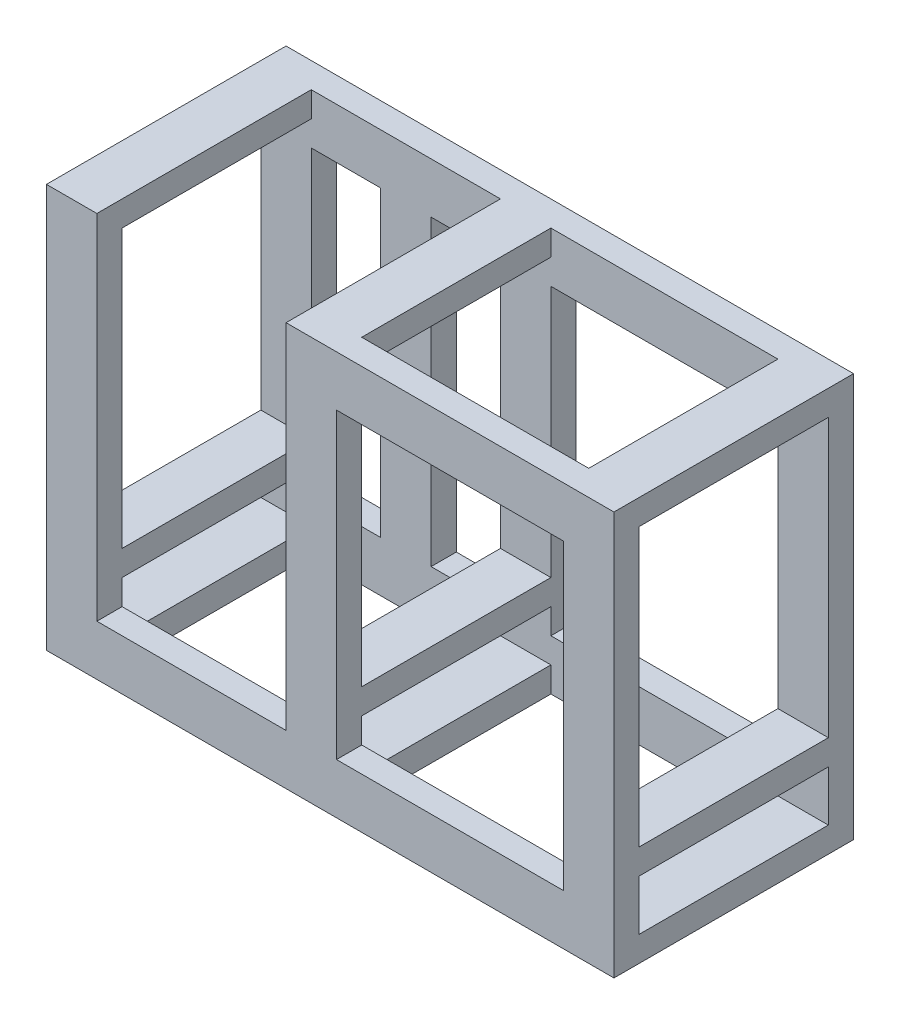
SolidWorks part; units mm, degrees
ref_plane "Front Plane" through (0, 0, 0) normal (0, 0, 1) x (1, 0, 0)
ref_plane "Top Plane" through (0, 0, 0) normal (0, 1, 0) x (1, 0, 0)
ref_plane "Right Plane" through (0, 0, 0) normal (1, 0, 0) x (0, 0, -1)
sketch "Sketch1" plane through (0, 0, 0) normal (0, 1, 0) x (1, 0, 0)
  line L1 (0, 0) -> (50.8, 0)
  line L2 (0, 0) -> (0, 25.4)
  line L3 (0, 25.4) -> (50.8, 25.4)
  line L4 (50.8, 0) -> (50.8, 25.4)
  line L5 (50.8, 0) -> (279.4, 0)
  line L6 (50.8, 0) -> (50.8, 25.4)
  line L7 (50.8, 25.4) -> (279.4, 25.4)
  line L8 (279.4, 0) -> (279.4, 25.4)
  line L9 (279.4, 0) -> (330.2, 0)
  line L10 (279.4, 0) -> (279.4, 25.4)
  line L11 (279.4, 25.4) -> (330.2, 25.4)
  line L12 (330.2, 0) -> (330.2, 25.4)
  line L13 (330.2, 25.4) -> (279.4, 25.4)
  line L14 (330.2, 25.4) -> (330.2, 215.9)
  line L15 (330.2, 215.9) -> (279.4, 215.9)
  line L16 (279.4, 25.4) -> (279.4, 215.9)
  line L17 (330.2, 215.9) -> (279.4, 215.9)
  line L18 (330.2, 215.9) -> (330.2, 241.3)
  line L19 (330.2, 241.3) -> (279.4, 241.3)
  line L20 (279.4, 215.9) -> (279.4, 241.3)
  line L21 (279.4, 241.3) -> (50.8, 241.3)
  line L22 (279.4, 241.3) -> (279.4, 215.9)
  line L23 (279.4, 215.9) -> (50.8, 215.9)
  line L24 (50.8, 241.3) -> (50.8, 215.9)
  line L25 (50.8, 241.3) -> (0, 241.3)
  line L26 (50.8, 241.3) -> (50.8, 215.9)
  line L27 (50.8, 215.9) -> (0, 215.9)
  line L28 (0, 241.3) -> (0, 215.9)
  line L29 (0, 215.9) -> (50.8, 215.9)
  line L30 (0, 215.9) -> (0, 25.4)
  line L31 (0, 25.4) -> (50.8, 25.4)
  line L32 (50.8, 215.9) -> (50.8, 25.4)
  line L33 (0, 25.4) -> (-190.5, 25.4)
  line L34 (0, 25.4) -> (0, 0)
  line L35 (0, 0) -> (-190.5, 0)
  line L36 (-190.5, 25.4) -> (-190.5, 0)
  line L37 (-190.5, 25.4) -> (-241.3, 25.4)
  line L38 (-190.5, 25.4) -> (-190.5, 0)
  line L39 (-190.5, 0) -> (-241.3, 0)
  line L40 (-241.3, 25.4) -> (-241.3, 0)
  line L41 (-241.3, 25.4) -> (-190.5, 25.4)
  line L42 (-241.3, 25.4) -> (-241.3, 215.9)
  line L43 (-241.3, 215.9) -> (-190.5, 215.9)
  line L44 (-190.5, 25.4) -> (-190.5, 215.9)
  line L45 (-241.3, 215.9) -> (-190.5, 215.9)
  line L46 (-241.3, 215.9) -> (-241.3, 241.3)
  line L47 (-241.3, 241.3) -> (-190.5, 241.3)
  line L48 (-190.5, 215.9) -> (-190.5, 241.3)
  line L49 (-190.5, 241.3) -> (0, 241.3)
  line L50 (-190.5, 241.3) -> (-190.5, 215.9)
  line L51 (-190.5, 215.9) -> (0, 215.9)
  line L52 (0, 241.3) -> (0, 215.9)
extrude "Boss-Extrude1" add sketch "Sketch1" along normal blind 50.8 contours L33 L36 L35 L2 | L48 L51 L28 L49 | L21 L24 L23 L20 | L5 L8 L7 L4 region at (-95.25, 0, -12.7) region at (165.1, 0, -12.7) region at (-95.25, 0, -228.6) region at (165.1, 0, -228.6)
extrude "Boss-Extrude2" add sketch "Sketch1<3>" along normal blind 25.4 contours L32 L27 L30 L3 | L16 L11 L14 L15 | L37 L44 L43 L42 region at (25.4, 0, -120.65) region at (-215.9, 0, -120.65) region at (304.8, 0, -120.65)
sketch "Sketch1<3>" plane through (0, 0, 0) normal (0, 1, 0) x (1, 0, 0) same geometry as "Sketch1"
extrude "Boss-Extrude3" add sketch "Sketch1<4>" along normal blind 406.4 contours L1 L4 L3 L2 | L25 L28 L27 L24 | L20 L15 L18 L19 | L9 L12 L11 L8 | L37 L40 L39 L36 | L43 L48 L47 L46 region at (25.4, 0, -12.7) region at (-215.9, 0, -12.7) region at (304.8, 0, -12.7) region at (25.4, 0, -228.6) region at (-215.9, 0, -228.6) region at (304.8, 0, -228.6)
sketch "Sketch1<4>" plane through (0, 0, 0) normal (0, 1, 0) x (1, 0, 0) same geometry as "Sketch1"
sketch "Sketch2" plane through (0, 406.4, 0) normal (0, 1, 0) x (1, 0, 0)
  line L1 (50.8, 25.4) -> (279.4, 25.4)
  line L2 (50.8, 25.4) -> (50.8, 0)
  line L3 (50.8, 0) -> (279.4, 0)
  line L4 (279.4, 25.4) -> (279.4, 0)
  line L5 (50.8, 25.4) -> (279.4, 0) construction
  line L6 (50.8, 0) -> (279.4, 25.4) construction
  line L7 (279.4, 25.4) -> (330.2, 25.4)
  line L8 (279.4, 25.4) -> (279.4, 215.9)
  line L9 (279.4, 215.9) -> (330.2, 215.9)
  line L10 (330.2, 25.4) -> (330.2, 215.9)
  line L11 (279.4, 25.4) -> (330.2, 215.9) construction
  line L12 (279.4, 215.9) -> (330.2, 25.4) construction
  line L13 (279.4, 241.3) -> (50.8, 241.3)
  line L14 (279.4, 241.3) -> (279.4, 215.9)
  line L15 (279.4, 215.9) -> (50.8, 215.9)
  line L16 (50.8, 241.3) -> (50.8, 215.9)
  line L17 (279.4, 241.3) -> (50.8, 215.9) construction
  line L18 (279.4, 215.9) -> (50.8, 241.3) construction
  line L19 (0, 215.9) -> (50.8, 215.9)
  line L20 (0, 215.9) -> (0, 25.4)
  line L21 (0, 25.4) -> (50.8, 25.4)
  line L22 (50.8, 215.9) -> (50.8, 25.4)
  line L23 (0, 215.9) -> (50.8, 25.4) construction
  line L24 (0, 25.4) -> (50.8, 215.9) construction
  line L25 (0, 241.3) -> (-190.5, 241.3)
  line L26 (0, 241.3) -> (0, 215.9)
  line L27 (0, 215.9) -> (-190.5, 215.9)
  line L28 (-190.5, 241.3) -> (-190.5, 215.9)
  line L29 (0, 241.3) -> (-190.5, 215.9) construction
  line L30 (0, 215.9) -> (-190.5, 241.3) construction
  line L31 (-241.3, 215.9) -> (-190.5, 215.9)
  line L32 (-241.3, 215.9) -> (-241.3, 25.4)
  line L33 (-241.3, 25.4) -> (-190.5, 25.4)
  line L34 (-190.5, 215.9) -> (-190.5, 25.4)
  line L35 (-241.3, 215.9) -> (-190.5, 25.4) construction
  line L36 (-241.3, 25.4) -> (-190.5, 215.9) construction
  line L37 (-120.65, 215.9) -> (-69.85, 215.9)
  line L38 (-120.65, 215.9) -> (-120.65, 241.3)
  line L39 (-120.65, 241.3) -> (-69.85, 241.3)
  line L40 (-69.85, 215.9) -> (-69.85, 241.3)
  line L41 (-120.65, 215.9) -> (-69.85, 241.3) construction
  line L42 (-120.65, 241.3) -> (-69.85, 215.9) construction
  point P4 (165.1, 12.7)
  point P10 (304.8, 120.65)
  point P15 (165.1, 228.6)
  point P21 (25.4, 120.65)
  point P25 (-95.25, 228.6)
  point P31 (-215.9, 120.65)
  point P34 (-95.25, 228.6)
  line M2 (50.8, 0) -> (50.8, 25.4)
  line M3 (50.8, 25.4) -> (0, 25.4)
extrude "Boss-Extrude8" add sketch "Sketch2" against normal blind 50.8 contours L13 L16 L15 L14 | L40 L27 L26 L25 | L27 L38 L25 L28 | L4 L1 L3 M2 region at (165.1, 406.4, -12.7) region at (-34.925, 406.4, -228.6) region at (165.1, 406.4, -228.6) region at (-155.575, 406.4, -228.6)
extrude "Boss-Extrude9" add sketch "Sketch2<3>" against normal blind 25.4 contours L22 L19 L20 M3 | L7 L10 L9 L8 | L34 L31 L32 L33 region at (-215.9, 406.4, -120.65) region at (25.4, 406.4, -120.65) region at (304.8, 406.4, -120.65)
sketch "Sketch2<3>" plane through (0, 406.4, 0) normal (0, 1, 0) x (1, 0, 0) same geometry as "Sketch2"
extrude "Boss-Extrude10" add sketch "Sketch2<4>" against normal up to surface (355.6 mm away) contours L27 L40 L25 L38 region at (-95.25, 406.4, -228.6) up to face at (-95.25, 50.8, -228.6)
sketch "Sketch2<4>" plane through (0, 406.4, 0) normal (0, 1, 0) x (1, 0, 0) same geometry as "Sketch2"
sketch "Sketch3" plane through (0, 0, -215.9) normal (0, 0, 1) x (1, 0, 0)
  line L0 (50.8, 0) -> (50.8, 76.2)
  line L1 (50.8, 355.6) -> (50.8, 50.8) construction
  line L2 (0, 355.6) -> (0, 50.8) construction
  line L3 (50.8, 76.2) -> (0, 76.2)
  line L4 (50.8, 76.2) -> (50.8, 101.6)
  line L5 (50.8, 101.6) -> (0, 101.6)
  line L6 (0, 76.2) -> (0, 101.6)
  line L7 (50.8, 76.2) -> (0, 101.6) construction
  line L8 (50.8, 101.6) -> (0, 76.2) construction
  line L9 (-190.5, 355.6) -> (-190.5, 50.8) construction
  line L10 (-190.5, 76.2) -> (-241.3, 76.2)
  line L11 (-190.5, 76.2) -> (-190.5, 101.6)
  line L12 (-190.5, 101.6) -> (-241.3, 101.6)
  line L13 (-241.3, 76.2) -> (-241.3, 101.6)
  line L14 (-190.5, 76.2) -> (-241.3, 101.6) construction
  line L15 (-190.5, 101.6) -> (-241.3, 76.2) construction
  line L16 (-241.3, 381) -> (-241.3, 25.4) construction
  line L17 (330.2, 381) -> (330.2, 25.4) construction
  line L18 (330.2, 76.2) -> (279.4, 76.2)
  line L19 (330.2, 76.2) -> (330.2, 101.6)
  line L20 (330.2, 101.6) -> (279.4, 101.6)
  line L21 (279.4, 76.2) -> (279.4, 101.6)
  line L22 (330.2, 76.2) -> (279.4, 101.6) construction
  line L23 (330.2, 101.6) -> (279.4, 76.2) construction
  line L24 (279.4, 355.6) -> (279.4, 50.8) construction
  point P8 (25.4, 88.9)
  point P15 (-215.9, 88.9)
  point P24 (304.8, 88.9)
  line M7 (330.2, 25.4) -> (330.2, 381)
  line M17 (-241.3, 381) -> (-241.3, 25.4)
  line M19 (-190.5, 50.8) -> (-190.5, 355.6)
  line M22 (0, 355.6) -> (0, 50.8)
  line M26 (50.8, 50.8) -> (50.8, 355.6)
  line M28 (279.4, 355.6) -> (279.4, 50.8)
extrude "Boss-Extrude11" add sketch "Sketch3" along normal up to surface (190.5 mm away) contours L12 L10 M19 M17 | L5 L3 M26 M22 | L20 L18 M7 M28 region at (25.4, 88.9, -215.9) region at (-215.9, 88.9, -215.9) region at (304.8, 88.9, -215.9) up to face at (165.1, 203.2, -25.4)
